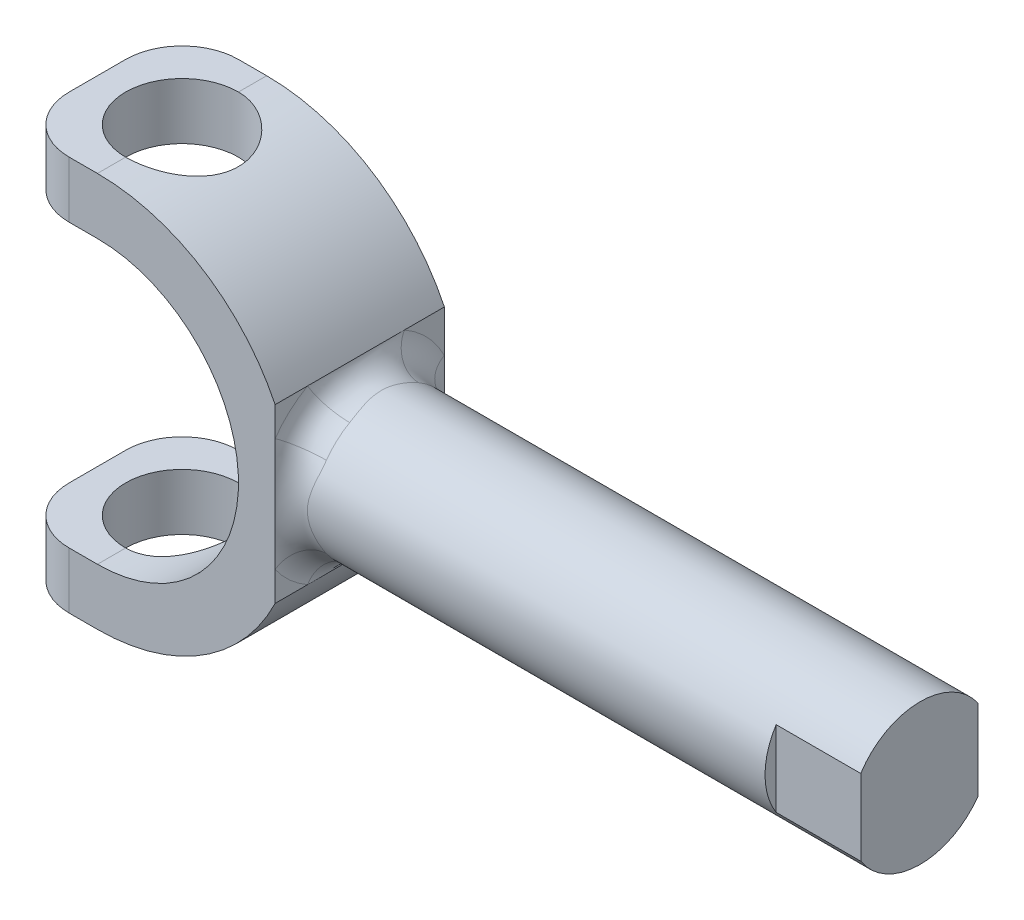
SolidWorks part; units mm, degrees
ref_plane "Front Plane" through (0, 0, 0) normal (0, 0, 1) x (1, 0, 0)
ref_plane "Top Plane" through (0, 0, 0) normal (0, 1, 0) x (1, 0, 0)
ref_plane "Right Plane" through (0, 0, 0) normal (1, 0, 0) x (0, 0, -1)
sketch "Sketch1" plane through (0, 0, 0) normal (0, 0, 1) x (1, 0, 0)
  line L3 (0, 35) -> (-15, 35)
  line L7 (31.5, 15.2561) -> (31.5, -15.2561)
  line L8 (-15, 25) -> (0, 25)
  line L9 (-15, 35) -> (-15, 25)
  line L10 (-15, -25) -> (-15, -35)
  line L11 (-15, -35) -> (0, -35)
  line L12 (0, -25) -> (-15, -25)
  arc A0 (0, -25) -> (0, 25) centre (0, 0) ccw
  arc A1 (0, -35) -> (31.5, -15.2561) centre (0, 0) ccw
  arc A2 (31.5, 15.2561) -> (0, 35) centre (0, 0) ccw
  dimension "D1" = 50
  dimension "D2" = 70
  dimension "D4" = 15
extrude "Boss-Extrude1" add sketch "Sketch1" along normal blind 30
sketch "Sketch2" plane through (0, 35, 0) normal (0, 1, 0) x (1, 0, 0)
  line L0 (0, -30) -> (0, 0) construction
  circle A0 centre (0, -15) radius 10
  dimension "D1" = 20
extrude "Cut-Extrude1" cut sketch "Sketch2" against normal blind 78
sketch "Sketch3" plane through (31.5, 0, 0) normal (1, 0, 0) x (0, 0, -1)
  circle A0 centre (-15.6641, 0) radius 12.5
  dimension "D1" = 25
extrude "Boss-Extrude2" add sketch "Sketch3" along normal blind 100
fillet "Fillet1" radius 5 1 edges at (31.5, 0, 3.1641)
fillet "Fillet2" radius 10 4 edges at (-15, 30, 0) (-15, 30, 30) (-15, -30, 0) (-15, -30, 30)
sketch "Sketch4" plane through (131.5, 0, 0) normal (1, 0, 0) x (0, 0, -1)
  line L1 (-33.1031, 7.8549) -> (-26.1953, 7.8549)
  line L2 (-33.1031, 7.8549) -> (-33.1031, -11.5697)
  line L3 (-33.1031, -11.5697) -> (-26.1953, -11.5697)
  line L4 (-26.1953, 7.8549) -> (-26.1953, -11.5697)
  line L5 (-2.1064, 8.1501) -> (-5.4127, 8.1501)
  line L6 (-2.1064, 8.1501) -> (-2.1064, -10.1527)
  line L7 (-2.1064, -10.1527) -> (-5.4127, -10.1527)
  line L8 (-5.4127, 8.1501) -> (-5.4127, -10.1527)
extrude "Cut-Extrude3" cut sketch "Sketch4" against normal blind 15
